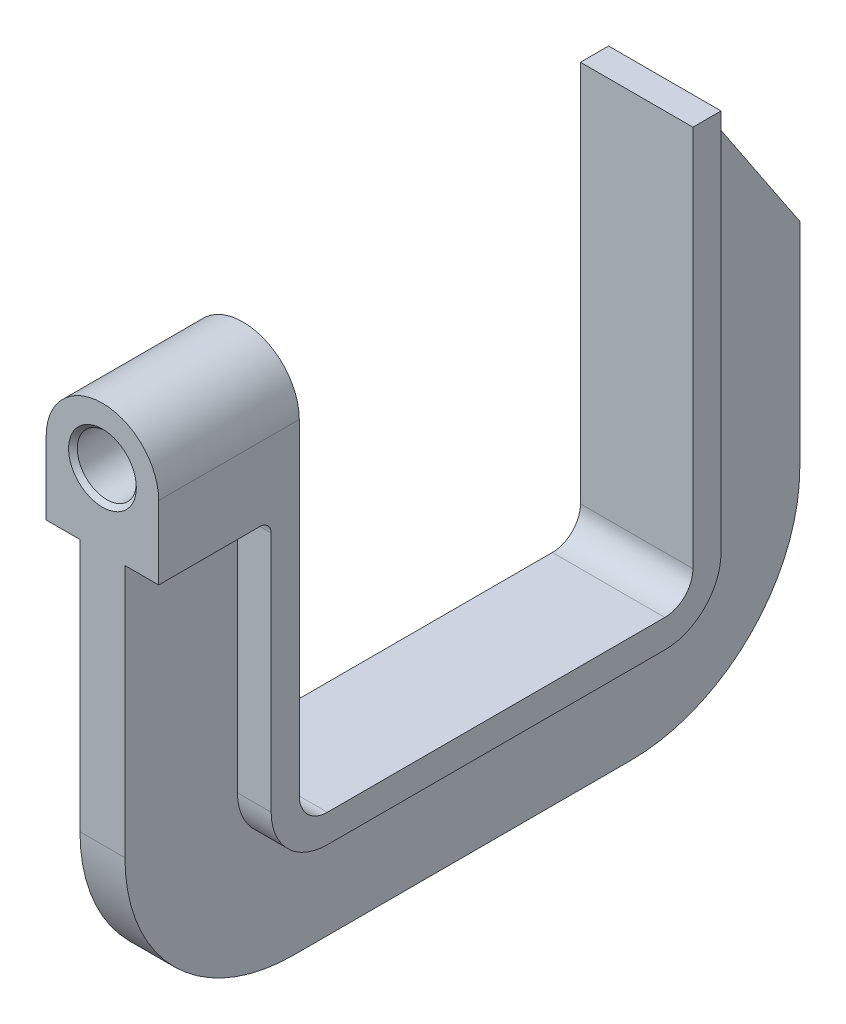
SolidWorks part; units mm, degrees
material "Gray Cast Iron"
ref_plane "Front Plane" through (0, 0, 0) normal (0, 0, 1) x (1, 0, 0)
ref_plane "Top Plane" through (0, 0, 0) normal (0, 1, 0) x (1, 0, 0)
ref_plane "Right Plane" through (0, 0, 0) normal (1, 0, 0) x (0, 0, -1)
sketch "Sketch1" plane through (0, 0, 0) normal (1, 0, 0) x (0, 0, -1)
  line L0 (0, 0) -> (0, -68)
  line L1 (-5, -73) -> (-65, -73)
  line L2 (-70, -68) -> (-70, 0)
  line L3 (5, 0) -> (5, -68)
  line L4 (-5, -78) -> (-65, -78)
  line L5 (-75, -68) -> (-75, 0)
  line L6 (0, 0) -> (5, 0)
  line L7 (-70, 0) -> (-75, 0)
  line L8 (5, 0) -> (25, -30)
  line L9 (25, -30) -> (25, -68)
  line L10 (-5, -98) -> (-65, -98)
  line L11 (-95, -68) -> (-95, 0)
  line L13 (-95, 0) -> (-75, 0)
  arc A0 (0, -68) -> (-5, -73) centre (-5, -68) cw
  arc A1 (-65, -73) -> (-70, -68) centre (-65, -68) cw
  arc A2 (5, -68) -> (-5, -78) centre (-5, -68) cw
  arc A3 (-65, -78) -> (-75, -68) centre (-65, -68) cw
  arc A4 (25, -68) -> (-5, -98) centre (-5, -68) cw
  arc A5 (-65, -98) -> (-95, -68) centre (-65, -68) cw
  arc A6 (0, -68) -> (-5, -73) centre (-5, -68) cw construction
  point P1 (-6.9951, -68)
  point P23 (25, -98)
  point P26 (-95, -98)
  point P27 (-5, -63.8184)
  point P29 (0, 0)
  dimension "D1" = 5
  dimension "D5" = 30
  dimension "D3" = 30
  dimension "D4" = 68
  dimension "D6" = 70
  dimension "D7" = 120
  dimension "D2" = 5
extrude "Boss-Extrude2" add sketch "Sketch1" along normal mid plane 8 contours A5 L10 A4 L9 L8 L3 A2 L4 A3 L5 L13 L11 region at (0, -15.8594, -13.7109)
extrude "Boss-Extrude3" add sketch "Sketch1<5>" along normal mid plane 20 contours A3 L4 A2 L3 L6 L0 A0 L1 A1 L2 L7 L5 region at (0, -1.1173, -2.5)
sketch "Sketch1<5>" plane through (0, 0, 0) normal (1, 0, 0) x (0, 0, -1) same geometry as "Sketch1"
sketch "Sketch2" plane through (0, 0, 95) normal (0, 0, 1) x (1, 0, 0)
  line L0 (-10, -10) -> (-10, -23)
  line L1 (-10, -68) -> (-10, 0) construction
  line L2 (-10, -23) -> (10, -23)
  line L3 (10, -68) -> (10, 0) construction
  line L4 (10, -23) -> (10, -10)
  arc A0 (10, -10) -> (-10, -10) centre (0, -10) ccw
  dimension "D1" = 23
extrude "Boss-Extrude6" add sketch "Sketch2" against normal up to surface (25 mm away) up to face at (0, -34, 70)
sketch "Sketch4" plane through (0, 0, 95) normal (0, 0, 1) x (1, 0, 0)
  line L0 (-10, -10) -> (-10, 0)
  line L1 (-10, 0) -> (10, 0)
  line L2 (10, 0) -> (10, -10)
  arc A0 (-10, -10) -> (10, -10) centre (0, -10) cw
  arc M4 (10, -10) -> (4, -0.8348) centre (0, -10) ccw
  line M5 (4, -0.8348) -> (4, 0)
  line M6 (4, 0) -> (-4, 0)
  line M7 (-4, 0) -> (-4, -0.8348)
  arc M8 (-4, -0.8348) -> (-10, -10) centre (0, -10) ccw
extrude "Cut-Extrude3" cut sketch "Sketch4" against normal up to surface (25 mm away) contours L2 L1 M5 M4 | L1 L0 M8 M7 | A0 L1 M7 | A0 M6 M5 region at (3.0085, -0.2486, 95) region at (-8.0219, -2.3403, 95) region at (-3.0085, -0.2486, 95) region at (8.0219, -2.3403, 95) up to face at (0, -34, 70)
hole_wizard "M12x1.5 Tapped Hole1" positions "Sketch6" profile "Sketch7" tap size "M12x1.5" standard "ANSI Metric" end condition up to next
sketch "Sketch6" plane through (0, 0, 95) normal (0, 0, 1) x (1, 0, 0)
  point P0 (0, -10)
sketch "Sketch7" plane through (0, -10, 95) normal (1, 0, 0) x (0, -1, 0)
  line L0 (0, 0) -> (0, 25)
  line L1 (0, 25) -> (5.25, 25)
  line L2 (5.25, 25) -> (5.25, 0.775)
  line L3 (5.25, 0.775) -> (6.025, 0)
  line L5 (6.025, 0) -> (0, 0)
  line L6 (-5.25, 0.775) -> (-6.025, 0) construction
  line L11 (0, -6.35) -> (0, 107.95) construction
  dimension "Thru Tap Drill Dia." = 10.5
  dimension "Thru Tap Drill Depth" = 25
  dimension "Near C'Sink Dia." = 12.05
  dimension "Near C'Sink Angle" = 90
cosmetic thread "Hole Thread1" parameters "D2"=12
fillet "Fillet1" radius 2 2 edges at (-7, -23, 75) (7, -23, 75)
